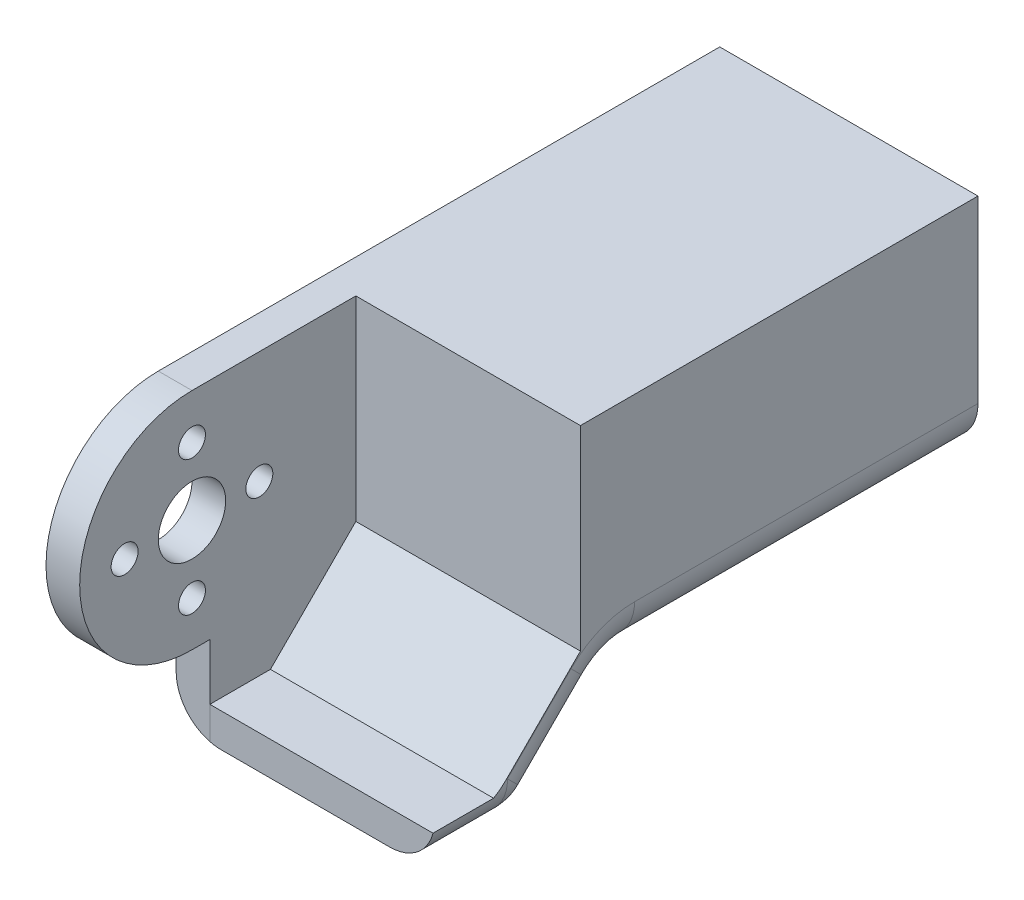
SolidWorks part; units mm, degrees
ref_plane "Front Plane" through (0, 0, 0) normal (0, 0, 1) x (1, 0, 0)
ref_plane "Top Plane" through (0, 0, 0) normal (0, 1, 0) x (1, 0, 0)
ref_plane "Right Plane" through (0, 0, 0) normal (1, 0, 0) x (0, 0, -1)
ref_plane "Plane1" through (15.5373, 0, 0) normal (1, 0, 0) x (0, 0, -1)
sketch "Sketch1" plane through (15.5373, 0, 0) normal (1, 0, 0) x (0, 0, -1)
  line L0 (-71.227, 229.327) -> (-119.6342, 229.327)
  line L1 (-119.6342, 229.327) -> (-119.6342, 201.327)
  line L2 (-119.6342, 201.327) -> (-71.227, 201.327)
  line L3 (-71.227, 201.327) -> (-71.227, 229.327)
extrude "Boss-Extrude1" add sketch "Sketch1" against normal blind 20
sketch "Sketch2" plane through (-4.4627, 0, 0) normal (-1, 0, 0) x (0, 0, 1)
  line L0 (71.227, 201.327) -> (71.227, 229.327)
  line L1 (71.227, 229.327) -> (121.227, 229.327)
  line L2 (121.227, 209.327) -> (119.6342, 209.327)
  line L3 (119.6342, 209.327) -> (119.6342, 201.327)
  line L4 (119.6342, 201.327) -> (71.227, 201.327)
  arc A0 (121.227, 229.327) -> (121.227, 209.327) centre (121.227, 219.327) cw
extrude "Boss-Extrude2" add sketch "Sketch2" along normal blind 3
sketch "Sketch3" plane through (15.5373, 0, 0) normal (1, 0, 0) x (0, 0, -1)
  line L0 (-106.6342, 211.9327) -> (-106.6342, 229.327)
  line L1 (-106.6342, 229.327) -> (-119.6342, 229.327)
  line L2 (-119.6342, 229.327) -> (-119.6342, 204.327)
  line L3 (-119.6342, 204.327) -> (-114.2399, 204.327)
  line L4 (-114.2399, 204.327) -> (-106.6342, 211.9327)
extrude "Cut-Extrude1" cut sketch "Sketch3" against normal blind 20
sketch "Sketch4" plane through (-7.4627, 0, 0) normal (-1, 0, 0) x (0, 0, 1)
  line L0 (71.227, 201.327) -> (111.4682, 201.327)
  line L1 (111.4682, 201.327) -> (103.4682, 209.327)
  line L2 (103.4682, 209.327) -> (71.227, 209.327)
  line L3 (71.227, 209.327) -> (71.227, 201.327)
extrude "Cut-Extrude2" cut sketch "Sketch4" against normal through all
hole_wizard "Ø6.0 (6) Diameter Hole1" positions "Sketch6" profile "Sketch5" hole size "Ø6.0" standard "ANSI Metric"
sketch "Sketch6" plane through (-4.4627, 0, 0) normal (1, 0, 0) x (0, 0, -1)
  point P0 (-121.227, 219.327)
sketch "Sketch5" plane through (-4.4627, 219.327, 121.227) normal (0, 1, 0) x (0, 0, -1)
  line L0 (0, 0) -> (0, 3)
  line L1 (0, 3) -> (3, 3)
  line L2 (3, 3) -> (3, 0)
  line L5 (3, 0) -> (0, 0)
  line L11 (0, -6.35) -> (0, 107.95) construction
  dimension "Thru Hole Dia." = 6
  dimension "Thru Hole Depth" = 3
hole_wizard "M2 Clearance Hole1" positions "Sketch8" profile "Sketch7" hole size "M2" standard "ANSI Metric" end condition through all
sketch "Sketch8" plane through (-7.4627, 0, 0) normal (-1, 0, 0) x (0, 0, 1)
  point P0 (121.227, 225.327)
  point P1 (127.227, 219.327)
  point P2 (121.227, 213.327)
  point P3 (115.227, 219.327)
sketch "Sketch7" plane through (-7.4627, 225.327, 121.227) normal (0, 1, 0) x (0, 0, 1)
  line L0 (0, 0) -> (0, 23)
  line L1 (0, 23) -> (1.2, 23)
  line L2 (1.2, 23) -> (1.2, 0.025)
  line L3 (1.2, 0.025) -> (1.225, 0)
  line L5 (1.225, 0) -> (0, 0)
  line L6 (-1.2, 0.025) -> (-1.225, 0) construction
  line L11 (0, -6.35) -> (0, 107.95) construction
  dimension "Thru Hole Dia." = 2.4
  dimension "Thru Hole Depth" = 23
  dimension "Near C'Sink Dia." = 2.45
  dimension "Near C'Sink Angle" = 90
fillet "Fillet1" radius 4 8 edges at (15.5373, 201.327, 115.5512) (15.5373, 209.327, 87.3476) (15.5373, 205.327, 107.4682) (-7.4627, 201.327, 115.5512) (4.0373, 201.327, 111.4682) (-7.4627, 205.327, 107.4682) (-7.4627, 209.327, 87.3476) (4.0373, 209.327, 103.4682) tangent propagation no
